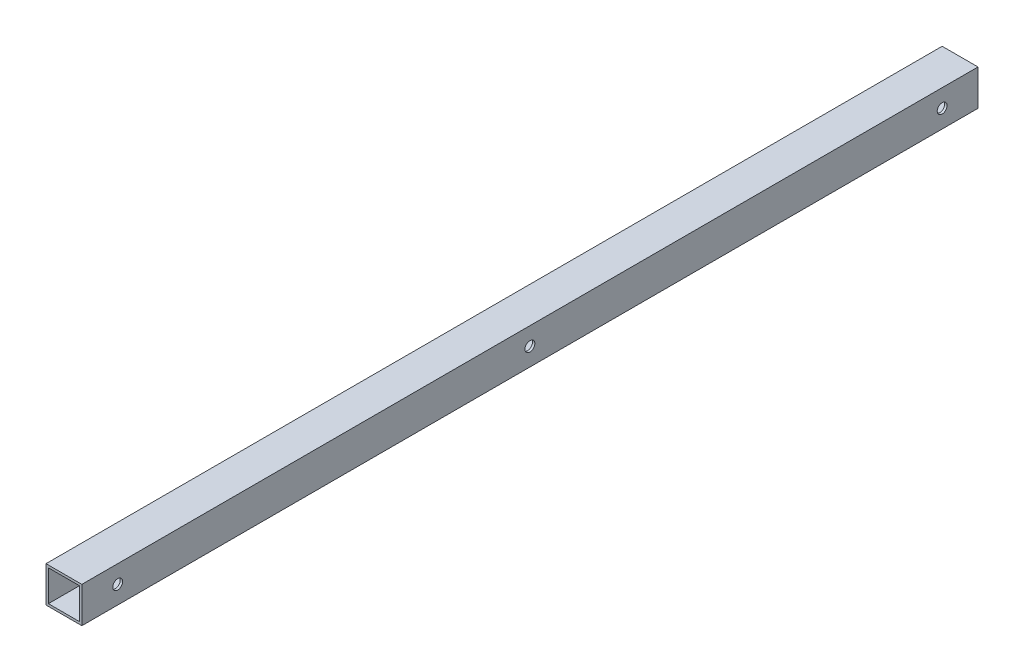
SolidWorks part; units mm, degrees
ref_plane "Спереди" through (0, 0, 0) normal (0, 0, 1) x (1, 0, 0)
ref_plane "Сверху" through (0, 0, 0) normal (0, 1, 0) x (1, 0, 0)
ref_plane "Справа" through (0, 0, 0) normal (1, 0, 0) x (0, 0, -1)
sketch "Эскиз1" plane through (0, 0, 0) normal (0, 0, 1) x (1, 0, 0)
  line L0 (0, 30) -> (2, 28)
  line L1 (0, 0) -> (30, 0)
  line L2 (0, 0) -> (0, 30)
  line L3 (0, 30) -> (30, 30)
  line L4 (30, 0) -> (30, 30)
  line L5 (30, 0) -> (28, 2)
  line L7 (2, 28) -> (28, 28)
  line L8 (2, 28) -> (2, 2)
  line L9 (2, 2) -> (28, 2)
  line L10 (28, 28) -> (28, 2)
  dimension "D1" = 2
  dimension "D2" = 2
  dimension "D3" = 2
  dimension "D4" = 2
  dimension "D5" = 30
extrude "Бобышка-Вытянуть1" add sketch "Эскиз1" along normal blind 750 contours L9 L8 L0 L2 L1 L5 | L7 L10 L5 L4 L3 L0 region at (15, 29.5757, 0) region at (0.7, 28.7, 0)
hole_wizard "Сверло под метчик  спиральное M81" positions "Эскиз2" profile "Эскиз3" hole size "M8x1.0" standard "DIN" end condition through all
sketch "Эскиз2" plane through (30, 0, 0) normal (1, 0, 0) x (0, 0, -1)
  line L0 (-750, 0) -> (-750, 30) construction
  line L1 (-750, 30) -> (0, 30) construction
  line L2 (-720, 15) -> (-375, 15) construction
  line L3 (-375, 15) -> (-30, 15) construction
  point P0 (-720, 15)
  point P2 (-375, 15)
  point P4 (-30, 15)
  point P10 (-750, 15)
  point P14 (-375, 30)
  dimension "D1" = 30
sketch "Эскиз3" plane through (30, 15, 720) normal (0, 1, 0) x (0, 0, -1)
  line L0 (0, 0) -> (0, 30)
  line L1 (0, 30) -> (4.125, 30)
  line L2 (4.125, 30) -> (4.125, 0)
  line L5 (4.125, 0) -> (0, 0)
  line L11 (0, -6.35) -> (0, 107.95) construction
  dimension "Диаметр сквозного отверстия" = 8.25
  dimension "Глубина сквозного отверстия" = 30
